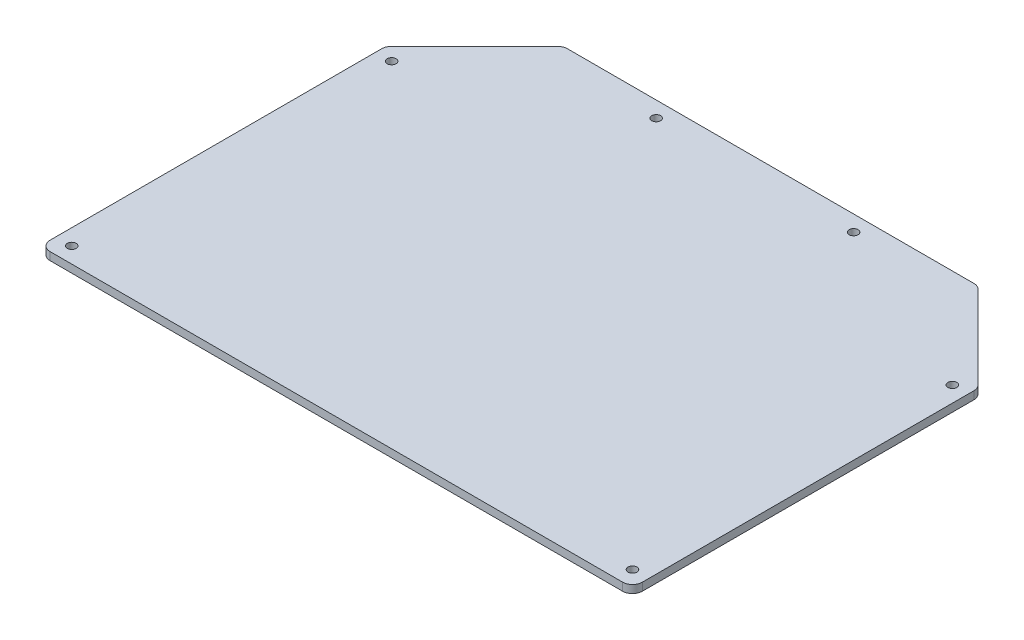
SolidWorks part; units mm, degrees
material "Acier non allié"
ref_plane "Front" through (0, 0, 0) normal (0, 0, 1) x (1, 0, 0)
ref_plane "Top" through (0, 0, 0) normal (0, 1, 0) x (1, 0, 0)
ref_plane "Right" through (0, 0, 0) normal (1, 0, 0) x (0, 0, -1)
sketch "Main scetch" plane through (0, 0, 0) normal (0, 1, 0) x (1, 0, 0)
  line L0 (-150, 0) -> (150, 0)
  line L1 (0, 0) -> (150, 0) construction
  line L2 (0, 0) -> (0, 220) construction
  line L3 (0, 220) -> (150, 220) construction
  line L4 (150, 0) -> (150, 220) construction
  line L5 (150, 0) -> (150, 175)
  line L6 (150, 175) -> (105, 220)
  line L10 (105, 220) -> (-105, 220)
  line L11 (-150, 0) -> (-150, 175)
  line L12 (-150, 175) -> (-105, 220)
  dimension "D1" = 150
  dimension "D2" = 220
  dimension "D3" = 45
  dimension "D4" = 45
extrude "Main extrusion" add sketch "Main scetch" along normal blind 4
fillet "Corner leave" radius 5 6 edges at (-150, 2, 0) (150, 2, -175) (105, 2, -220) (150, 2, 0) (-105, 2, -220) (-150, 2, -175)
sketch "Esquisse1" plane through (0, 4, 0) normal (0, 1, 0) x (1, 0, 0)
  line L0 (-145, 0) -> (145, 0) construction
  line L1 (-150, 172.9289) -> (-150, 5) construction
  line L2 (102.9289, 220) -> (-102.9289, 220) construction
  line L4 (150, 5) -> (150, 172.9289) construction
  circle A0 centre (-142, 8) radius 1
  circle A1 centre (-142, 170) radius 1
  circle A2 centre (-50, 212) radius 1
  circle A3 centre (50, 212) radius 1
  circle A4 centre (142, 170) radius 1
  circle A5 centre (142, 8) radius 1
  point P16 (0, 0)
  point P21 (150, 171.7475)
  dimension "D3" = 2
  dimension "D6" = 2
  dimension "D8" = 2
  dimension "D11" = 2
  dimension "D15" = 2
  dimension "D18" = 2
  dimension "D1" = 8
  dimension "D2" = 8
  dimension "D4" = 8
  dimension "D5" = 170
  dimension "D7" = 8
  dimension "D9" = 50
  dimension "D10" = 50
  dimension "D12" = 8
  dimension "D13" = 170
  dimension "D14" = 8
  dimension "D16" = 8
  dimension "D17" = 8
hole_wizard "Dégagement M41" positions "Esquisse2" profile "Esquisse3" hole size "M4" standard "ISO" end condition through all
sketch "Esquisse2" plane through (0, 4, 0) normal (0, 1, 0) x (1, 0, 0)
  point P0 (-142, 8)
  point P3 (-142, 170)
  point P6 (-50, 212)
  point P9 (50, 212)
  point P12 (142, 170)
  point P15 (142, 8)
sketch "Esquisse3" plane through (-142, 4, -8) normal (1, 0, 0) x (0, 0, 1)
  line L0 (0, 0) -> (0, 4)
  line L1 (0, 4) -> (2.25, 4)
  line L2 (2.25, 4) -> (2.25, 0)
  line L5 (2.25, 0) -> (0, 0)
  line L11 (0, -6.35) -> (0, 107.95) construction
  dimension "Diamètre du perçage jusqu'au prochain" = 4.5
  dimension "Profondeur du perçage jusqu'au prochain" = 4
equation "\"WIDTH\"= 300mm'Total width of the robot"
equation "\"LENGTH\"= 220mm'Total length of the robot"
equation "\"D1@Main scetch\" = \"WIDTH\" / 2"
equation "\"D2@Main scetch\" = \"LENGTH\""
equation "\"CUT_DEPTH\"= 45mm'Depth of the cut on the edges of the plate"
equation "\"D3@Main scetch\" = \"CUT_DEPTH\""
equation "\"D4@Main scetch\" = \"CUT_DEPTH\""
equation "\"Plate_th\"= 3mm'Thickness of the plate"
equation "\"D1\"= \"Plate_th\""
